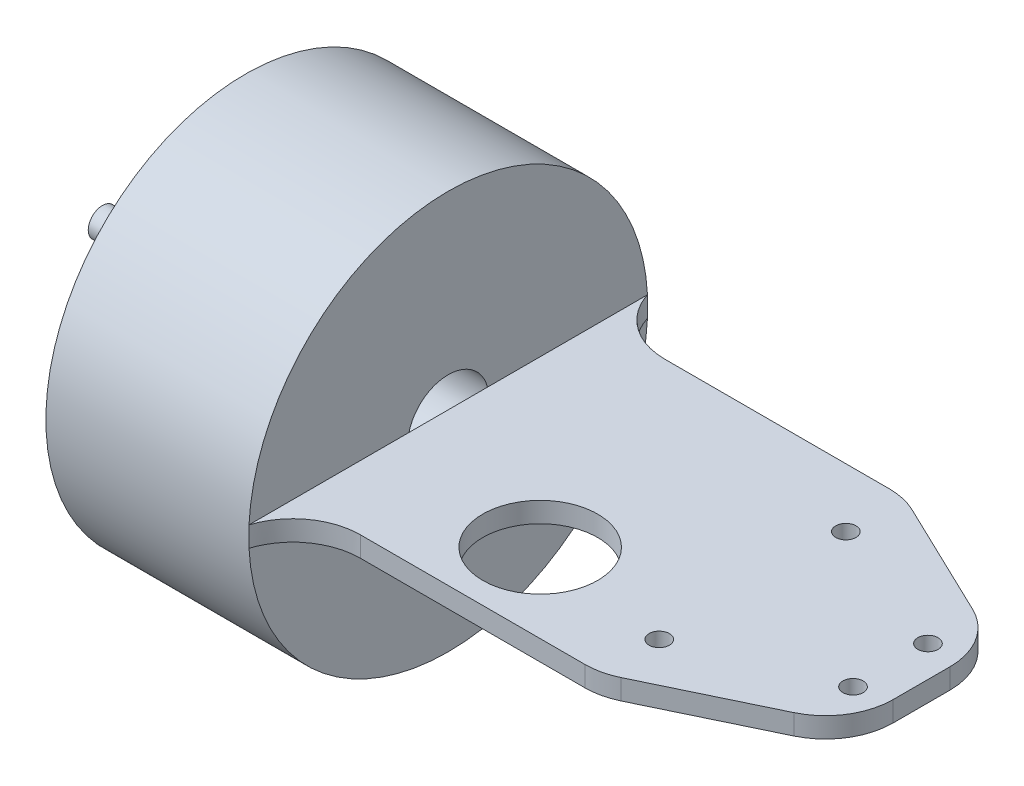
SolidWorks part; units mm, degrees
ref_plane "Front Plane" through (0, 0, 0) normal (0, 0, 1) x (1, 0, 0)
ref_plane "Top Plane" through (0, 0, 0) normal (0, 1, 0) x (1, 0, 0)
ref_plane "Right Plane" through (0, 0, 0) normal (1, 0, 0) x (0, 0, -1)
sketch "Sketch1" plane through (12.0257, 0, 0) normal (1, 0, 0) x (0, 0, -1)
  circle A0 centre (-52.0844, 35.3462) radius 29.5 construction
  circle A1 centre (-52.0844, 35.3462) radius 29.5
  circle A2 centre (-52.0844, 35.3462) radius 6 construction
  circle A3 centre (-52.0844, 35.3462) radius 6
  circle A4 centre (-63.2213, 46.4831) radius 2.1 construction
  circle A5 centre (-63.2213, 46.4831) radius 2.1 construction
  circle A6 centre (-63.2213, 24.2093) radius 2.1 construction
  circle A7 centre (-63.2213, 24.2093) radius 2.1 construction
  circle A10 centre (-40.9474, 24.2093) radius 2.1 construction
  circle A11 centre (-40.9474, 24.2093) radius 2.1 construction
  circle A12 centre (-40.9474, 46.4831) radius 2.1 construction
  circle A13 centre (-40.9474, 46.4831) radius 2.1 construction
extrude "Boss-Extrude1" add sketch "Sketch1" along normal blind 30
sketch "Sketch2" plane through (12.0257, 0, 0) normal (-1, 0, 0) x (0, 0, 1)
  circle A0 centre (40.9474, 24.2093) radius 2.1 construction
  circle A1 centre (63.2213, 24.2093) radius 2.1 construction
  circle A2 centre (63.2213, 46.4831) radius 2.1 construction
  circle A3 centre (40.9474, 46.4831) radius 2.1 construction
  circle A4 centre (40.9474, 24.2093) radius 2.1
  circle A5 centre (63.2213, 24.2093) radius 2.1
  circle A6 centre (63.2213, 46.4831) radius 2.1
  circle A7 centre (40.9474, 46.4831) radius 2.1
extrude "Boss-Extrude2" add sketch "Sketch2" along normal blind 10
sketch "Sketch3" plane through (42.0257, 0, 0) normal (1, 0, 0) x (0, 0, -1)
  line L0 (-52.0844, 64.8462) -> (-52.0844, 5.8462) construction
  line L1 (-74.5844, 33.8462) -> (-29.5844, 33.8462)
  line L2 (-74.5844, 33.8462) -> (-74.5844, 36.8462)
  line L3 (-74.5844, 36.8462) -> (-29.5844, 36.8462)
  line L4 (-29.5844, 33.8462) -> (-29.5844, 36.8462)
  circle A0 centre (-52.0844, 35.3462) radius 29.5 construction
  point P12 (-52.0844, 33.8462)
  point P13 (-74.5844, 35.3462)
  dimension "D1" = 45
  dimension "D2" = 3
extrude "Boss-Extrude3" add sketch "Sketch3" along normal blind 70
ref_axis "Axis1" through (42.0257, 36.8462, 52.0844) along (1, 0, 0)
ref_plane "Plane1" through (0, 0, 52.0844) normal (0, 0, 1) x (1, 0, 0)
fillet "Fillet1" radius 10 4 edges at (42.0257, 35.3462, 74.5844) (42.0257, 35.3462, 29.5844) (112.0257, 35.3462, 29.5844) (112.0257, 35.3462, 74.5844)
sketch "Sketch4" plane through (0, 36.8462, 0) normal (0, 1, 0) x (1, 0, 0)
  line L0 (112.0257, -52.0844) -> (5.4522, -52.0844) construction
  line L1 (112.0257, -39.5844) -> (112.0257, -64.5844) construction
  circle A0 centre (87.0257, -38.2844) radius 1.5
  circle A1 centre (87.0257, -65.8844) radius 1.5
  circle A2 centre (66.4257, -62.8844) radius 8.5
  circle A3 centre (107.4257, -46.5444) radius 1.5
  circle A4 centre (107.4257, -57.6244) radius 1.5
  dimension "D1" = 3
  dimension "D2" = 3
  dimension "D7" = 17
  dimension "D5" = 3
  dimension "D10" = 3
  dimension "D3" = 13.8
  dimension "D4" = 13.8
  dimension "D6" = 25
  dimension "D8" = 20.6
  dimension "D9" = 3
  dimension "D11" = 20.4
  dimension "D12" = 8.26
  dimension "D13" = 8.26
extrude "Cut-Extrude1" cut sketch "Sketch4" against normal up to next
sketch "Sketch5" plane through (0, 36.8462, 0) normal (0, 1, 0) x (1, 0, 0)
  line L0 (87.0257, -29.5844) -> (112.0257, -41.5844)
  line L1 (102.0257, -29.5844) -> (51.5542, -29.5844) construction
  line L2 (112.0257, -39.5844) -> (112.0257, -64.5844) construction
  line L3 (112.0257, -41.5844) -> (112.0257, -23.5844)
  line L4 (112.0257, -23.5844) -> (87.0257, -23.5844)
  line L5 (87.0257, -23.5844) -> (87.0257, -29.5844)
  dimension "D1" = 25
  dimension "D2" = 18
  dimension "D3" = 6
extrude "Cut-Extrude2" cut sketch "Sketch5" against normal up to next
mirror "Mirror1" about plane through (0, 0, 52.0844) normal (0, 0, 1) of "Cut-Extrude2"
fillet "Fillet2" radius 10 4 edges at (87.0257, 35.3462, 29.5844) (112.0257, 35.3462, 41.5844) (112.0257, 35.3462, 62.5844) (87.0257, 35.3462, 74.5844)
